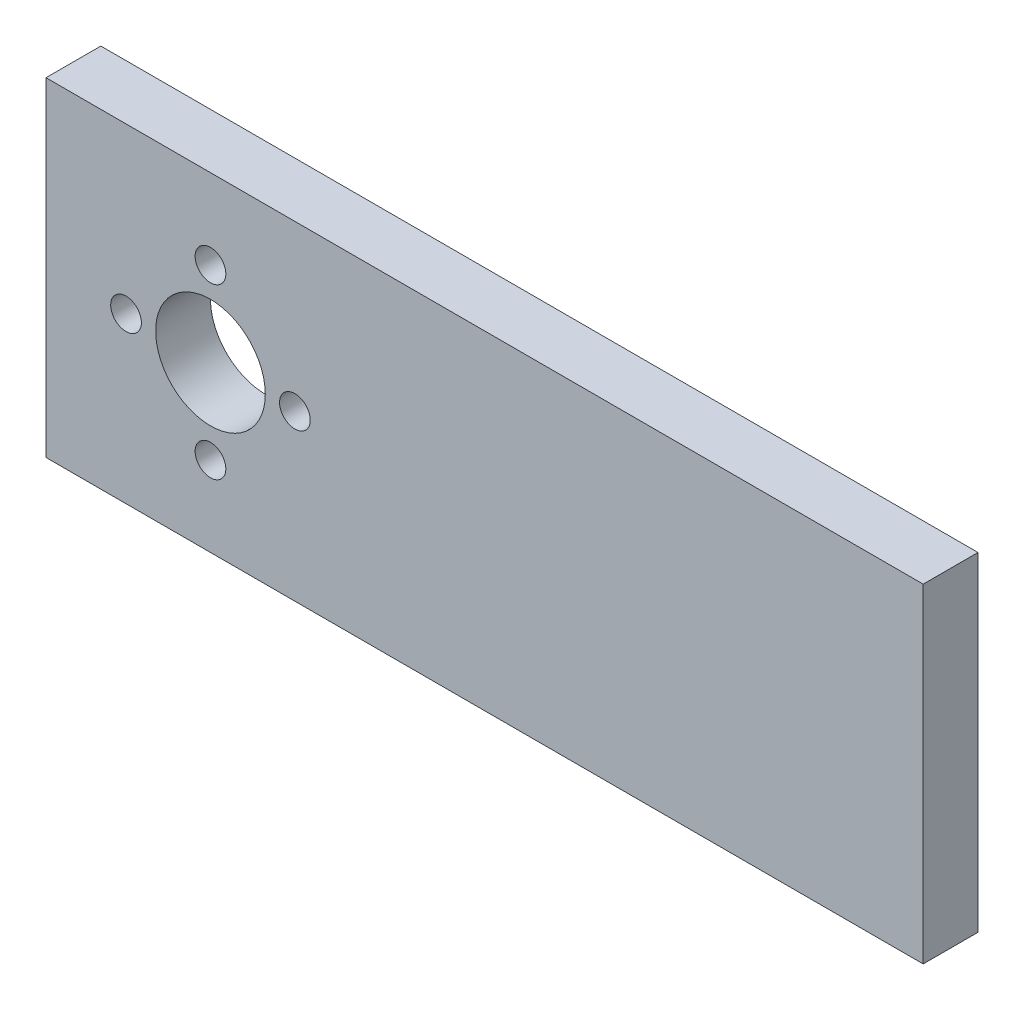
SolidWorks part; units mm, degrees
material "PET"
ref_plane "Front Plane" through (0, 0, 0) normal (0, 0, 1) x (1, 0, 0)
ref_plane "Top Plane" through (0, 0, 0) normal (0, 1, 0) x (1, 0, 0)
ref_plane "Right Plane" through (0, 0, 0) normal (1, 0, 0) x (0, 0, -1)
sketch "Sketch1" plane through (0, 0, 0) normal (0, 0, 1) x (1, 0, 0)
  line L1 (0, 0) -> (101.6, 0)
  line L2 (0, 0) -> (0, -38.1)
  line L3 (0, -38.1) -> (101.6, -38.1)
  line L4 (101.6, 0) -> (101.6, -38.1)
  dimension "D1" = 101.6
  dimension "D2" = 38.1
extrude "Boss-Extrude1" add sketch "Sketch1" along normal blind 6.35
sketch "Sketch2" plane through (0, 0, 6.35) normal (0, 0, 1) x (1, 0, 0)
  line L0 (101.6, -38.1) -> (101.6, 0) construction
  line L1 (0, -38.1) -> (101.6, -38.1) construction
  circle A0 centre (19.05, -19.05) radius 6.35
  dimension "D1" = 82.55
  dimension "D3" = 12.7
  dimension "D2" = 19.05
extrude "Cut-Extrude1" cut sketch "Sketch2" against normal blind 6.35
sketch "Sketch3" plane through (0, 0, 6.35) normal (0, 0, 1) x (1, 0, 0)
  line L0 (101.6, -38.1) -> (101.6, 0) construction
  circle A0 centre (19.05, -28.829) radius 1.778
  circle A1 centre (19.05, -19.05) radius 6.35 construction
  dimension "D1" = 82.55
  dimension "D2" = 3.556
  dimension "D3" = 9.779
extrude "Cut-Extrude2" cut sketch "Sketch3" against normal blind 6.35
pattern_circular "CirPattern1" count 4 over 360 about axis through (19.05, -19.05, 6.35) along (0, 0, 1) of "Cut-Extrude2"
